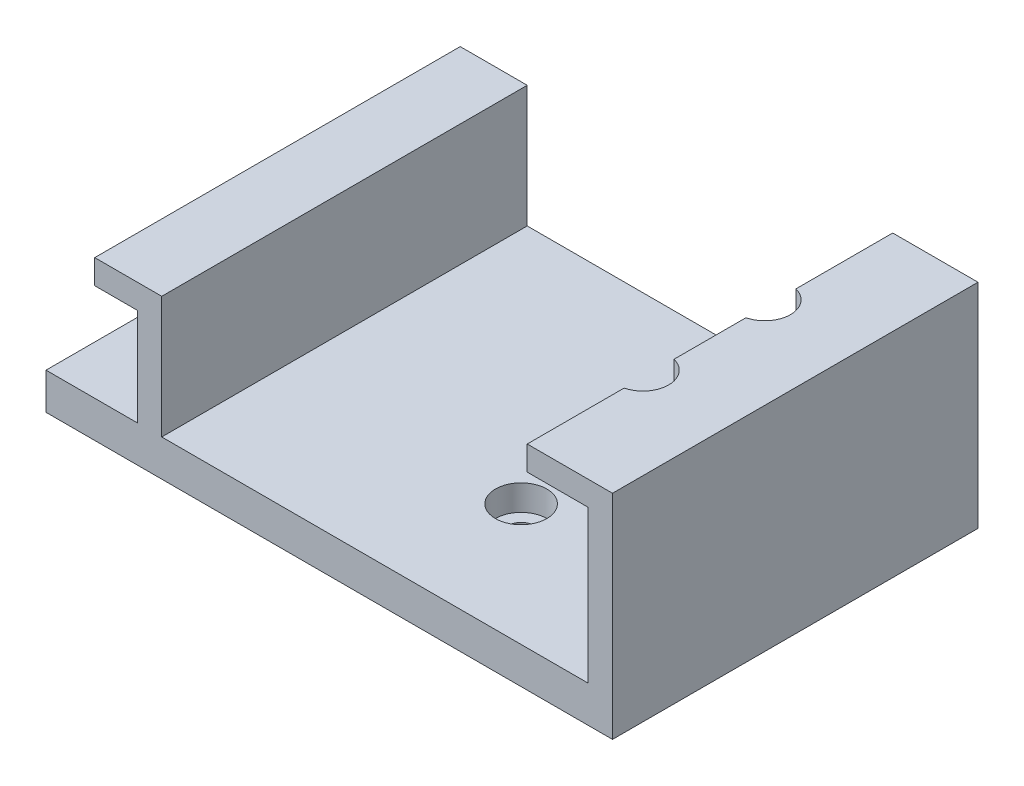
SolidWorks part; units mm, degrees
ref_plane "Front Plane" through (0, 0, 0) normal (0, 0, 1) x (1, 0, 0)
ref_plane "Top Plane" through (0, 0, 0) normal (0, 1, 0) x (1, 0, 0)
ref_plane "Right Plane" through (0, 0, 0) normal (1, 0, 0) x (0, 0, -1)
sketch "Sketch1" plane through (0, 0, 0) normal (0, 0, 1) x (1, 0, 0)
  line L0 (-14, 0) -> (0, 0)
  line L1 (0, 0) -> (0, -35)
  line L2 (0, -35) -> (-93, -35)
  line L3 (-93, -35) -> (-93, -29)
  line L4 (-93, -29) -> (-78, -29)
  line L5 (-78, -29) -> (-78, -13)
  line L6 (-78, -13) -> (-85, -13)
  line L7 (-85, -13) -> (-85, -9)
  line L8 (-85, -9) -> (-74, -9)
  line L9 (-74, -9) -> (-74, -29)
  line L10 (-74, -29) -> (-4, -29)
  line L11 (-4, -29) -> (-4, -4)
  line L12 (-4, -4) -> (-14, -4)
  line L13 (-14, -4) -> (-14, 0)
  dimension "D1" = 25
  dimension "D2" = 70
  dimension "D3" = 6
  dimension "D4" = 6
  dimension "D5" = 4
  dimension "D6" = 4
  dimension "D7" = 4
  dimension "D8" = 4
  dimension "D9" = 10
  dimension "D10" = 16
  dimension "D11" = 7
  dimension "D12" = 15
extrude "Extrude-Base" add sketch "Sketch1" along normal blind 60
sketch "Sketch2" plane through (0, -29, 0) normal (0, 1, 0) x (1, 0, 0)
  line L0 (-15, -40) -> (-15, -20) construction
  line L1 (-15, -20) -> (-35, -20) construction
  line L2 (-35, -20) -> (-35, -40) construction
  line L3 (-35, -40) -> (-15, -40) construction
  line L4 (0, -60) -> (0, 0) construction
  line L5 (0, -30) -> (-35, -30) construction
  circle A0 centre (-15, -40) radius 2.2
  circle A1 centre (-15, -20) radius 2.2
  circle A2 centre (-35, -20) radius 2.2
  circle A3 centre (-35, -40) radius 2.2
  point P6 (-15, -30)
  point P9 (0, -30)
  dimension "D4" = 4.4
  dimension "D5" = 4.4
  dimension "D6" = 4.4
  dimension "D7" = 4.4
  dimension "D1" = 15
  dimension "D2" = 20
  dimension "D3" = 20
extrude "Cut-Bolt Holes" cut sketch "Sketch2" against normal blind 10
sketch "Sketch3" plane through (0, -29, 0) normal (0, 1, 0) x (1, 0, 0)
  circle A0 centre (-35, -20) radius 4.215
  circle A1 centre (-15, -20) radius 4.215
  circle A2 centre (-15, -40) radius 4.215
  circle A3 centre (-35, -40) radius 4.215
  circle A4 centre (-35, -40) radius 2.2 construction
  circle A5 centre (-15, -40) radius 2.2 construction
  circle A6 centre (-15, -20) radius 2.2 construction
  circle A7 centre (-35, -20) radius 2.2 construction
  dimension "D1" = 8.43
  dimension "D2" = 8.43
  dimension "D3" = 8.43
  dimension "D4" = 8.43
extrude "Cut-Bolt Head Insets" cut sketch "Sketch3" against normal blind 4.2 and the other way blind 40
sketch "Sketch4" plane through (-93, 0, 0) normal (-1, 0, 0) x (0, 0, 1)
  line L0 (60, -35) -> (0, -35) construction
  line L1 (50, -35) -> (10, -35)
  line L2 (50, -35) -> (50, -32)
  line L3 (50, -32) -> (10, -32)
  line L4 (10, -35) -> (10, -32)
  point P6 (-35.8142, -35)
  point P7 (30, -35)
  point P8 (30, -35)
  dimension "D1" = 40
  dimension "D2" = 3
extrude "Cut-Top Clearance Slot" cut sketch "Sketch4" against normal blind 45
fillet "Fillet-Clearance Slot Pt 1" radius 3 2 edges at (-70.5, -32, 50) (-70.5, -32, 10)
fillet "Fillet-Clearance Slot Pt 2" radius 3 2 edges at (-70.5, -35, 50) (-70.5, -35, 10)
equation "\"holeBoltDiam\"=4.4"
equation "\"D4@Sketch2\"=\"holeBoltDiam\""
equation "\"D5@Sketch2\"=\"holeBoltDiam\""
equation "\"D6@Sketch2\"=\"holeBoltDiam\""
equation "\"D7@Sketch2\"=\"holeBoltDiam\""
equation "\"insetBoltHead\"=8.43"
equation "\"D1@Sketch3\"=\"insetBoltHead\""
equation "\"D2@Sketch3\"=\"insetBoltHead\""
equation "\"D3@Sketch3\"=\"insetBoltHead\""
equation "\"D4@Sketch3\"=\"insetBoltHead\""
